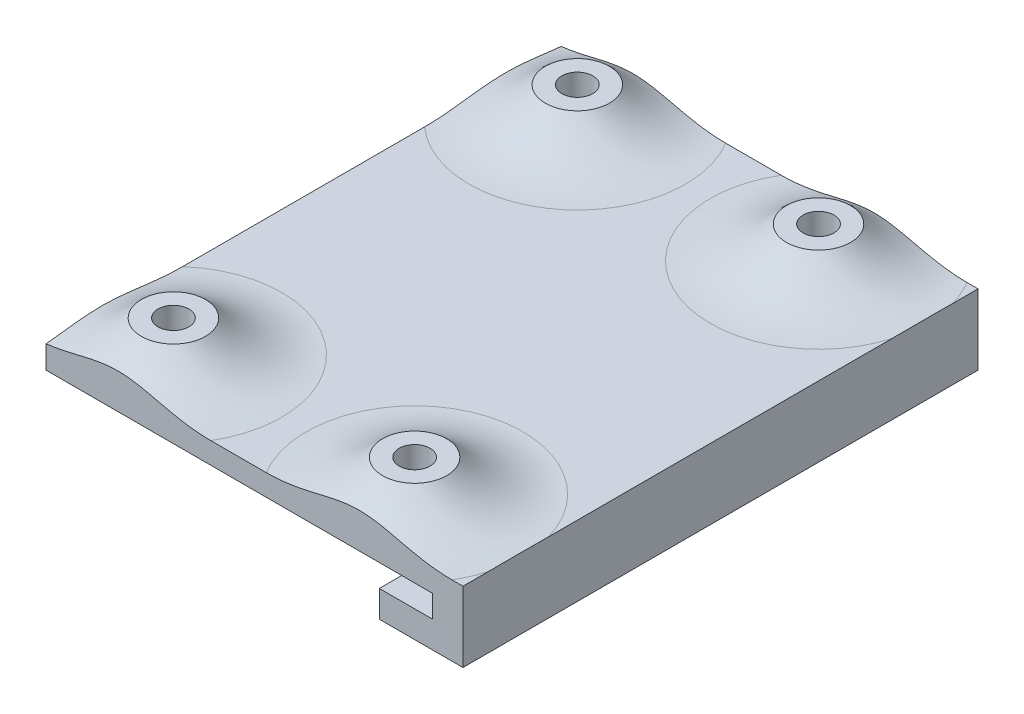
SolidWorks part; units mm, degrees
ref_plane "Front Plane" through (0, 0, 0) normal (0, 0, 1) x (1, 0, 0)
ref_plane "Top Plane" through (0, 0, 0) normal (0, 1, 0) x (1, 0, 0)
ref_plane "Right Plane" through (0, 0, 0) normal (1, 0, 0) x (0, 0, -1)
sketch "Esquisse1" plane through (0, 0, 0) normal (0, 1, 0) x (1, 0, 0)
  line L1 (-18.034, 24.13) -> (18.034, 24.13)
  line L2 (-18.034, 24.13) -> (-18.034, -24.13)
  line L3 (-18.034, -24.13) -> (18.034, -24.13)
  line L4 (18.034, 24.13) -> (18.034, -24.13)
  line L5 (-18.034, 24.13) -> (18.034, -24.13) construction
  line L6 (-18.034, -24.13) -> (18.034, 24.13) construction
  point P0 (0, 0)
extrude "Boss.-Extru.1" add sketch "Esquisse1" along normal blind 2
ref_plane "Plan1" through (0, 0, 0) normal (1, 0, 0) x (0, 0, -1)
sketch "Esquisse4" plane through (0, 2, 0) normal (0, 1, 0) x (1, 0, 0)
  line L0 (0, -8.2401) -> (0, 8.2401) construction
  line L1 (18.034, -24.13) -> (18.034, 24.13) construction
  circle A0 centre (11.3, 18.921) radius 3
  circle A1 centre (11.3, -18.925) radius 3
  point P7 (18.034, 0)
  dimension "D1" = 37.846
  dimension "D3" = 11.3
  dimension "D4" = 11.3
  dimension "D2" = 18.925
extrude "Boss.-Extru.2" add sketch "Esquisse4" along normal blind 3
sketch "Esquisse6" plane through (0, 5, 0) normal (0, 1, 0) x (1, 0, 0)
  circle A0 centre (11.3, 18.921) radius 1.45
  circle A1 centre (11.3, -18.925) radius 1.45
extrude "Enlèv. mat.-Extru.1" cut sketch "Esquisse6" against normal through all
mirror "Symétrie1" about plane through (0, 0, 0) normal (1, 0, 0) of "Boss.-Extru.2", "Enlèv. mat.-Extru.1"
sketch "Esquisse10" plane through (18.034, 0, 0) normal (1, 0, 0) x (0, 0, -1)
  line L1 (24.13, 2) -> (-24.13, 2)
  line L2 (24.13, 2) -> (24.13, 0)
  line L3 (24.13, 0) -> (-24.13, 0)
  line L4 (-24.13, 2) -> (-24.13, 0)
extrude "Boss.-Extru.3" add sketch "Esquisse10" along normal blind 3
sketch "Esquisse11" plane through (0, 0, 0) normal (0, -1, 0) x (-1, 0, 0)
  line L0 (18.034, -24.13) -> (-21.034, -24.13) construction
  line L1 (-21.034, 24.13) -> (-18.1944, 24.13)
  line L2 (-21.034, 24.13) -> (-21.034, -24.13)
  line L3 (-21.034, -24.13) -> (-18.1944, -24.13)
  line L4 (-18.1944, 24.13) -> (-18.1944, -24.13)
extrude "Boss.-Extru.4" add sketch "Esquisse11" along normal blind 4.6
sketch "Esquisse12" plane through (18.1944, 0, 0) normal (-1, 0, 0) x (0, 0, 1)
  line L0 (-24.13, -4.6) -> (-24.13, 0) construction
  line L1 (24.13, -4.6) -> (-24.13, -4.6)
  line L2 (24.13, -4.6) -> (24.13, -2.1)
  line L3 (24.13, -2.1) -> (-24.13, -2.1)
  line L4 (-24.13, -4.6) -> (-24.13, -2.1)
extrude "Boss.-Extru.5" add sketch "Esquisse12" along normal blind 5
fillet "Congé1" radius 10 2 edges at (-11.3, 2, -15.921) (-11.3, 2, 21.925)
fillet "Congé2" radius 10 2 edges at (11.3, 2, 21.925) (11.3, 2, -15.921)
